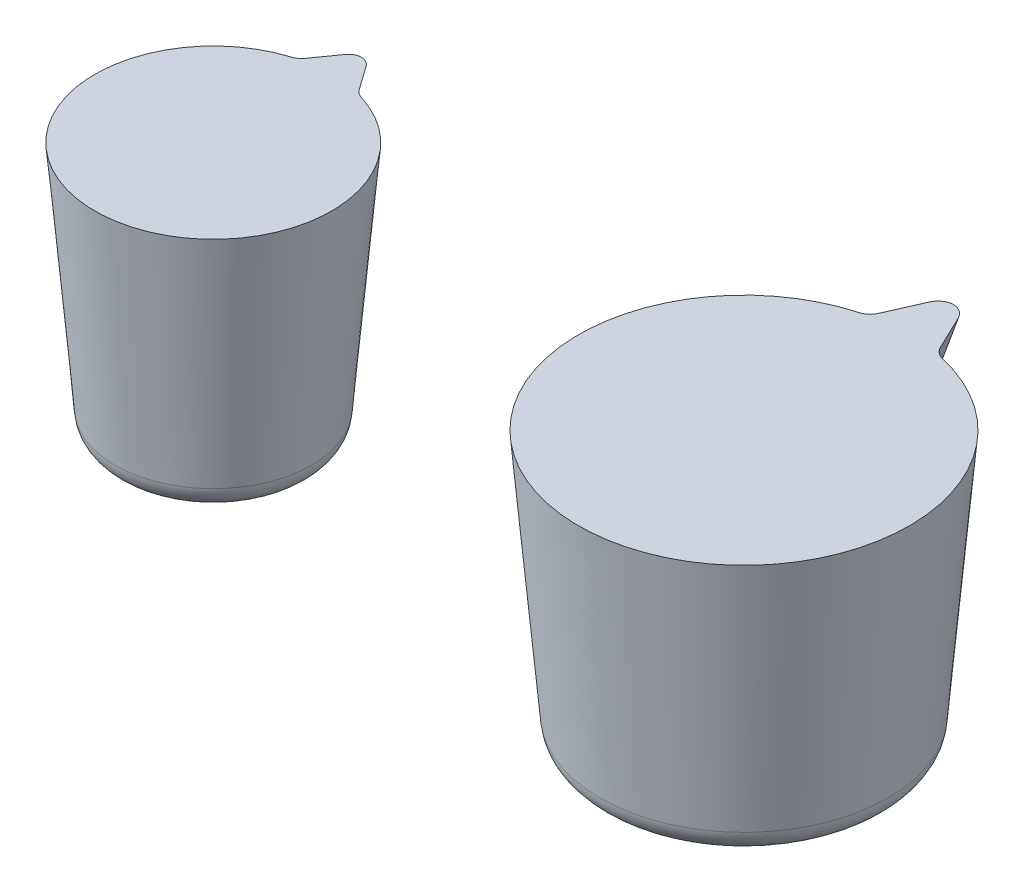
SolidWorks part; units mm, degrees
ref_plane "Front" through (0, 0, 0) normal (0, 0, 1) x (1, 0, 0)
ref_plane "Top" through (0, 0, 0) normal (0, 1, 0) x (1, 0, 0)
ref_plane "Right" through (0, 0, 0) normal (1, 0, 0) x (0, 0, -1)
other "Configuration Table"
sketch "Sketch2" plane through (0, 0, 0) normal (0, 1, 0) x (1, 0, 0)
  circle A0 centre (-60.7304, 0) radius 17.7145
extrude "Extrude1" add sketch "Sketch2" along normal blind 47 draft 5 draft outward yes
sketch "Sketch3" plane through (0, 0, 0) normal (0, 1, 0) x (1, 0, 0)
  circle A0 centre (37.0756, 0) radius 26.1266
extrude "Extrude2" add sketch "Sketch3" along normal blind 50 draft 5 draft outward yes
fillet "Fillet1" radius 5 1 edges at (-60.7304, 0, 17.7145)
fillet "Fillet2" radius 5 1 edges at (37.0756, 0, 26.1266)
sketch "Sketch5" plane through (0, 50, 0) normal (0, 1, 0) x (-1, 0, 0)
  line L0 (-37.0756, 0) -> (60.7304, 0) construction
ref_plane "Plane1" through (0, 37.5, -21.6506) normal (0, 0.866, -0.5) x (-1, 0, 0)
sketch "Sketch6" plane through (0, 37.5, -21.6506) normal (0, 0.866, -0.5) x (-1, 0, 0)
  line L0 (-47.3646, 7.653) -> (-36.2106, -12.4863)
  line L1 (-36.2106, -12.4863) -> (-25.986, 7.653)
  line L2 (-47.3646, 7.653) -> (-25.986, 7.653)
  line L3 (-36.2106, -12.4863) -> (-36.6753, 7.653) construction
extrude "Extrude5" add sketch "Sketch6" along normal up to surface and the other way up to surface
fillet "Fillet5" radius 3 3 edges at (36.2106, 36.9375, -35.7438)
sketch "Sketch8" plane through (0, 37.5, -21.6506) normal (0, 0.866, -0.5) x (-1, 0, 0)
  line L0 (51.1463, 10.1442) -> (60.7304, -1.5655)
  line L1 (60.7304, -1.5655) -> (70.3145, 10.1442)
  line L2 (51.1463, 10.1442) -> (70.3145, 10.1442)
  line L3 (60.7304, -1.5655) -> (60.7304, 10.1442) construction
extrude "Extrude6" add sketch "Sketch8" along normal up to surface and the other way up to surface
fillet "Fillet6" radius 2.5 3 edges at (-60.7304, 39.7361, -24.7493)
sketch "Sketch4" plane through (0, 0, 0) normal (1, 0, 0) x (0, 0, -1)
  line L0 (0, 21.5542) -> (0, 37.0006) construction
  line L1 (0, 27.5) -> (0, -27.5) construction
  line L2 (-8.4047, 37.0006) -> (8.4047, 37.0006)
  line L3 (8.4047, 37.0006) -> (4.3159, 17.9197)
  line L4 (-8.4047, 37.0006) -> (-4.3159, 17.9197)
  line L5 (4.3159, 17.9197) -> (-4.3159, 17.9197)
